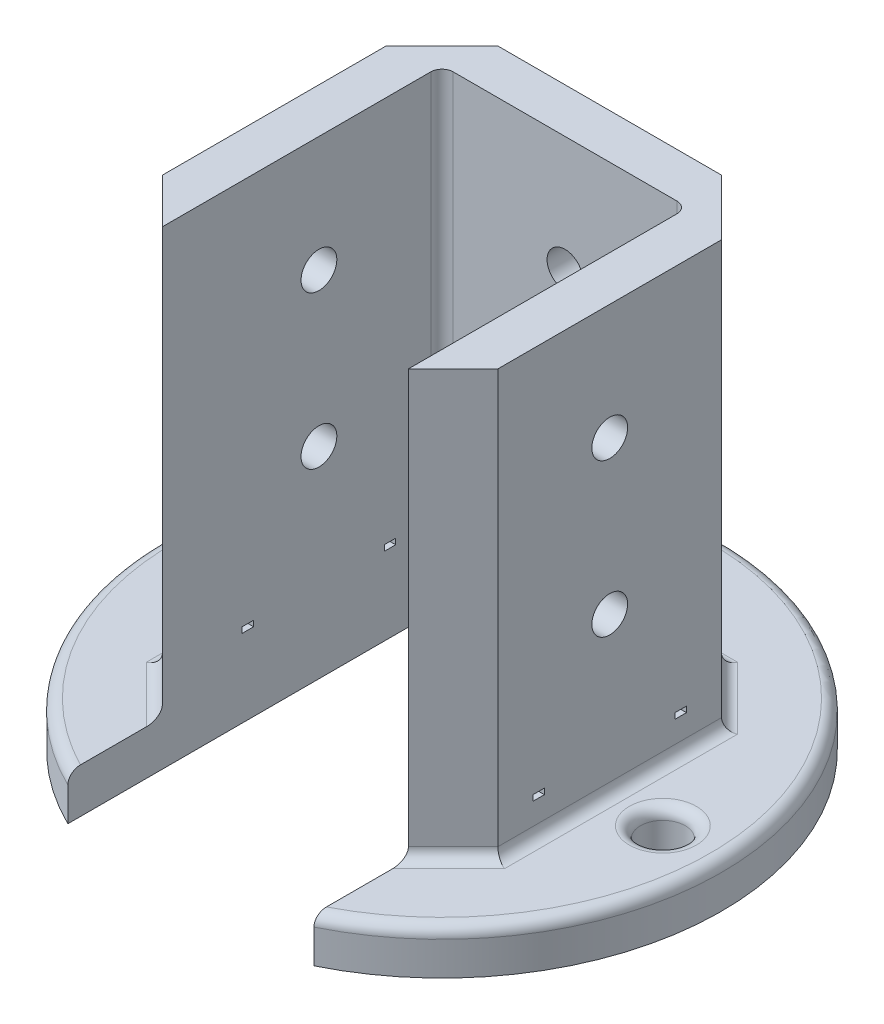
SolidWorks part; units mm, degrees
ref_plane "Front Plane" through (0, 0, 0) normal (0, 0, 1) x (1, 0, 0)
ref_plane "Top Plane" through (0, 0, 0) normal (0, 1, 0) x (1, 0, 0)
ref_plane "Right Plane" through (0, 0, 0) normal (1, 0, 0) x (0, 0, -1)
sketch "Sketch1" plane through (0, 0, 0) normal (0, 1, 0) x (1, 0, 0)
  line L1 (0, 0) -> (30, 0)
  line L2 (0, 0) -> (0, 30)
  line L3 (0, 30) -> (30, 30)
  line L4 (30, 0) -> (30, 30)
  dimension "D1" = 30
  dimension "D2" = 30
extrude "Boss-Extrude1" add sketch "Sketch1" along normal blind 62
shell "Shell1" thickness 4 removed face at (15, 0, -15) removed face at (15, 62, -15)
sketch "Sketch2" plane through (30, 0, 0) normal (1, 0, 0) x (0, 0, -1)
  line L0 (0, 0) -> (30, 0) construction
  circle A0 centre (15, 14) radius 1.6
  circle A2 centre (15, 27.66) radius 1.6
  point P4 (15, 26.06)
  point P7 (15, 15.6)
  point P8 (15, 0)
  dimension "D1" = 3.2
  dimension "D2" = 3.2
  dimension "D3" = 10.46
  dimension "D4" = 14
extrude "Cut-Extrude1" cut sketch "Sketch2" against normal blind 62
sketch "Sketch3" plane through (0, 0, 0) normal (0, -1, 0) x (1, 0, 0)
  line L0 (26, -26) -> (4, -26) construction
  line L9 (30, 0) -> (30, -30) construction
  line L11 (26, -4) -> (26, -26) construction
  line L12 (4, -26) -> (4, -4) construction
  line L13 (4, -4) -> (26, -4) construction
  line L14 (26, -26) -> (4, -26)
  line L15 (26, -4) -> (26, -26)
  line L16 (4, -26) -> (4, -4)
  line L17 (4, -4) -> (26, -4)
  circle A0 centre (15, -15) radius 25
  circle A1 centre (34.75, -15) radius 2
  circle A8 centre (15, -34.75) radius 2
  circle A9 centre (-4.75, -15) radius 2
  circle A10 centre (15, 4.75) radius 2
  point P7 (26, -15)
  point P15 (15, -26)
  point P23 (16.25, -11.25)
  point P24 (15, -15)
  dimension "D1" = 50
  dimension "D2" = 4
  dimension "D3" = 4.75
  dimension "D4" = 4
extrude "Boss-Extrude2" add sketch "Sketch3" along normal blind 4
pattern_circular "CirPattern1" count 2 over 90 about axis through (15, -4, -15) along (0, 1, 0) of "Cut-Extrude1"
chamfer "Chamfer1" distance 5 angle 45 4 edges at (0, 31, 0) (30, 31, 0) (30, 31, -30) (0, 31, -30)
fillet "Fillet1" radius 1 12 edges at (15, 62, -4) (26, 62, -15) (15, 62, -26) (4, 62, -15) (2.5, 62, -27.5) (15, 62, -30) (27.5, 62, -27.5) (30, 62, -15) (27.5, 62, -2.5) (15, 62, 0) (2.5, 62, -2.5) (0, 62, -15)
fillet "Fillet2" radius 1 13 edges at (34.75, 0, -17) (15, 0, -40) (2.5, 0, -2.5) (15, 0, 0) (27.5, 0, -2.5) (30, 0, -15) (27.5, 0, -27.5) (15, 0, -30) (2.5, 0, -27.5) (0, 0, -15) (15, 0, 2.75) (-4.75, 0, -17) (15, 0, -36.75)
sketch "Sketch4" plane through (4, 0, 0) normal (1, 0, 0) x (0, 0, -1)
  line L0 (8.14, 3.46) -> (9.16, 3.46)
  line L1 (9.16, 3.46) -> (9.16, 2.95)
  line L2 (9.16, 2.95) -> (8.14, 2.95)
  line L3 (8.14, 2.95) -> (8.14, 3.46)
  line L12 (21.86, 2.95) -> (21.86, 3.46)
  line L13 (21.86, 3.46) -> (20.84, 3.46)
  line L14 (20.84, 3.46) -> (20.84, 2.95)
  line L15 (20.84, 2.95) -> (21.86, 2.95)
extrude "Cut-Extrude2" cut sketch "Sketch4" against normal through all both and the other way through all
pattern_circular "CirPattern2" count 2 over 90 about axis through (15, -4, -15) along (0, -1, 0) of "Cut-Extrude2"
sketch "Sketch5" plane through (0, 62, 0) normal (0, 1, 0) x (1, 0, 0)
  line L1 (4, 4) -> (26, 4)
  line L2 (4, 4) -> (4, -10.9141)
  line L3 (4, -10.9141) -> (26, -10.9141)
  line L4 (26, 4) -> (26, -10.9141)
extrude "Cut-Extrude3" cut sketch "Sketch5" against normal through all
sketch "Sketch6" plane through (0, 0, 0) normal (-1, 0, 0) x (0, 0, 1)
  line L0 (-5, 1) -> (-5, 61) construction
  line L1 (-25, 58) -> (-5, 58)
  line L2 (-25, 58) -> (-25, 43)
  line L3 (-25, 43) -> (-5, 43)
  line L4 (-5, 58) -> (-5, 43)
  line L5 (-5, 61) -> (-25, 61) construction
  dimension "D1" = 18
  dimension "D2" = 3
extrude "Cut-Extrude4" cut sketch "Sketch6" against normal through all and the other way through all
sketch "Sketch7" plane through (0, 0, -30) normal (0, 0, -1) x (-1, 0, 0)
  line L0 (-5, 1) -> (-5, 61) construction
  line L1 (-25, 58) -> (-5, 58)
  line L2 (-25, 58) -> (-25, 43)
  line L3 (-25, 43) -> (-5, 43)
  line L4 (-5, 58) -> (-5, 43)
  line L5 (-5, 61) -> (-25, 61) construction
  dimension "D1" = 18
  dimension "D2" = 3
extrude "Cut-Extrude5" cut sketch "Sketch7" against normal through all contours L1 L4 L3 L2
fillet "Fillet4" radius 1 12 edges at (2, 43, -5) (2, 58, -5) (2, 58, -25) (2, 43, -25) (25, 43, -28) (25, 58, -28) (28, 58, -25) (28, 43, -25) (5, 43, -28) (5, 58, -28) (28, 58, -5) (28, 43, -5)
sketch "Sketch8" plane through (0, 0, 0) normal (-1, 0, 0) x (0, 0, 1)
  line L0 (-24.5858, 62) -> (-5.4142, 62) construction
  line L1 (-34.6564, 38) -> (5.0381, 38)
  line L2 (-34.6564, 38) -> (-34.6564, 62)
  line L3 (-34.6564, 62) -> (5.0381, 62)
  line L4 (5.0381, 38) -> (5.0381, 62)
  dimension "D1" = 24
  dimension "D2" = 0
extrude "Cut-Extrude6" cut sketch "Sketch8" against normal through all
fillet "Fillet5" radius 1 2 edges at (26, 17, -26) (4, 17, -26)
